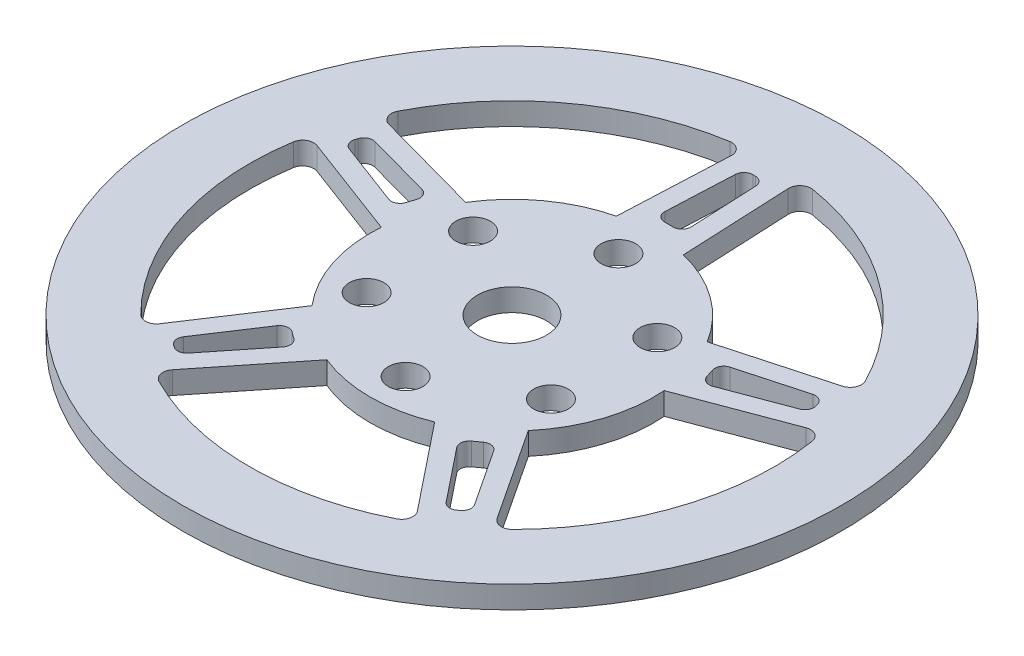
SolidWorks part; units mm, degrees
ref_plane "Front Plane" through (0, 0, 0) normal (0, 0, 1) x (1, 0, 0)
ref_plane "Top Plane" through (0, 0, 0) normal (0, 1, 0) x (1, 0, 0)
ref_plane "Right Plane" through (0, 0, 0) normal (1, 0, 0) x (0, 0, -1)
sketch "Sketch1" plane through (0, 0, 0) normal (0, 1, 0) x (1, 0, 0)
  line L0 (0, 0) -> (0, -9.525) construction
  line L1 (0, 0) -> (8.2489, -4.7625) construction
  line L2 (0, 0) -> (8.2489, 4.7625) construction
  line L3 (0, 0) -> (0, 33.015) construction
  line L4 (0, 0) -> (31.3992, 10.2022) construction
  line L5 (0, 0) -> (19.4058, -26.7097) construction
  line L6 (0, 0) -> (-19.4058, -26.7097) construction
  line L7 (0, 0) -> (-31.3992, 10.2022) construction
  line L8 (-2.5, 23.3666) -> (2.5, 23.3666) construction
  line L9 (-3, 12.3406) -> (3, 12.3406) construction
  line L10 (-2.5, 23.3666) -> (-3, 12.3406)
  line L11 (2.5, 23.3666) -> (3, 12.3406)
  line L12 (-0.8753, 21.6666) -> (0.8753, 21.6666)
  line L13 (0.8753, 21.6666) -> (1.2212, 14.0406)
  line L14 (1.2212, 14.0406) -> (-1.2212, 14.0406)
  line L15 (-1.2212, 14.0406) -> (-0.8753, 21.6666)
  line L16 (21.4505, 9.5983) -> (10.8095, 6.6666)
  line L17 (12.976, 5.5002) -> (20.3357, 7.5279)
  line L18 (20.8767, 5.8629) -> (13.7307, 3.1774)
  line L19 (20.3357, 7.5279) -> (20.8767, 5.8629)
  line L20 (13.7307, 3.1774) -> (12.976, 5.5002)
  line L21 (22.9955, 4.843) -> (12.6636, 0.9603)
  line L22 (15.7571, -17.4345) -> (9.6807, -8.2204)
  line L23 (9.2408, -10.6413) -> (13.4435, -17.0142)
  line L24 (12.0272, -18.0432) -> (7.2649, -12.0769)
  line L25 (13.4435, -17.0142) -> (12.0272, -18.0432)
  line L26 (7.2649, -12.0769) -> (9.2408, -10.6413)
  line L27 (11.712, -20.3735) -> (4.8266, -11.7471)
  line L28 (-11.712, -20.3735) -> (-4.8266, -11.7471)
  line L29 (-7.2649, -12.0769) -> (-12.0272, -18.0432)
  line L30 (-13.4435, -17.0142) -> (-9.2408, -10.6413)
  line L31 (-12.0272, -18.0432) -> (-13.4435, -17.0142)
  line L32 (-9.2408, -10.6413) -> (-7.2649, -12.0769)
  line L33 (-15.7571, -17.4345) -> (-9.6807, -8.2204)
  line L34 (-22.9955, 4.843) -> (-12.6636, 0.9603)
  line L35 (-13.7307, 3.1774) -> (-20.8767, 5.8629)
  line L36 (-20.3357, 7.5279) -> (-12.976, 5.5002)
  line L37 (-20.8767, 5.8629) -> (-20.3357, 7.5279)
  line L38 (-12.976, 5.5002) -> (-13.7307, 3.1774)
  line L39 (-21.4505, 9.5983) -> (-10.8095, 6.6666)
  line L40 (0, 0) -> (-8.2489, -4.7625) construction
  line L41 (0, 0) -> (-8.2489, 4.7625) construction
  circle A0 centre (0, 0) radius 12.7 construction
  circle A1 centre (0, 9.525) radius 1.55
  circle A2 centre (-8.2489, 4.7625) radius 1.55
  circle A3 centre (-8.2489, -4.7625) radius 1.55
  circle A4 centre (0, -9.525) radius 1.55
  circle A5 centre (0, 0) radius 29.5
  circle A6 centre (8.2489, 4.7625) radius 1.55
  circle A7 centre (0, 0) radius 3.1
  circle A8 centre (8.2489, -4.7625) radius 1.55
  circle A9 centre (0, 0) radius 23.5 construction
  arc A10 (-3, 12.3406) -> (-10.8095, 6.6666) centre (0, 0) ccw
  arc A11 (10.8095, 6.6666) -> (3, 12.3406) centre (0, 0) ccw
  arc A12 (9.6807, -8.2204) -> (12.6636, 0.9603) centre (0, 0) ccw
  arc A13 (4.8266, -11.7471) -> (-4.8266, -11.7471) centre (0, 0) cw
  arc A14 (-12.6636, 0.9603) -> (-9.6807, -8.2204) centre (0, 0) ccw
  arc A15 (-21.4505, 9.5983) -> (-2.5, 23.3666) centre (0, 0) cw
  arc A16 (2.5, 23.3666) -> (21.4505, 9.5983) centre (0, 0) cw
  arc A17 (22.9955, 4.843) -> (15.7571, -17.4345) centre (0, 0) cw
  arc A18 (11.712, -20.3735) -> (-11.712, -20.3735) centre (0, 0) cw
  arc A19 (-15.7571, -17.4345) -> (-22.9955, 4.843) centre (0, 0) cw
  point P25 (0, 0)
  point P66 (0, 0)
  dimension "D1" = 3.1
  dimension "D2" = 3.1
  dimension "D5" = 59
  dimension "D6" = 47
  dimension "D9" = 25.4
  dimension "D16" = 6.2
  dimension "D17" = 3.1
  dimension "D18" = 3.1
  dimension "D19" = 3.1
  dimension "D20" = 3.1
  dimension "D21" = 9.525
  dimension "D3" = 60
  dimension "D4" = 60
  dimension "D8" = 2.5
  dimension "D10" = 3
  dimension "D11" = 1.7
  dimension "D12" = 9.525
  dimension "D13" = 1.7
  dimension "D14" = 1.7
  dimension "D22" = 9.525
  dimension "D23" = 9.525
  dimension "D24" = 9.525
  dimension "D25" = 9.525
  dimension "D26" = 60
  dimension "D27" = 60
  dimension "D7" = 5
  dimension "D15" = 5
extrude "Boss-Extrude1" add sketch "Sketch1" along normal blind 2
fillet "Fillet2" radius 1 10 edges at (-15.7571, 1, 17.4345) (-11.712, 1, 20.3735) (11.712, 1, 20.3735) (15.7571, 1, 17.4345) (22.9955, 1, -4.843) (21.4505, 1, -9.5983) (2.5, 1, -23.3666) (-2.5, 1, -23.3666) (-22.9955, 1, -4.843) (-21.4505, 1, -9.5983)
fillet "Fillet3" radius 0.8 20 edges at (-20.8767, 1, -5.8629) (-20.3357, 1, -7.5279) (-12.976, 1, -5.5002) (-13.7307, 1, -3.1774) (-12.0272, 1, 18.0432) (-13.4435, 1, 17.0142) (-9.2408, 1, 10.6413) (-7.2649, 1, 12.0769) (13.4435, 1, 17.0142) (12.0272, 1, 18.0432) (7.2649, 1, 12.0769) (9.2408, 1, 10.6413) (12.976, 1, -5.5002) (20.3357, 1, -7.5279) (20.8767, 1, -5.8629) (13.7307, 1, -3.1774) (-0.8753, 1, -21.6666) (0.8753, 1, -21.6666) (-1.2212, 1, -14.0406) (1.2212, 1, -14.0406)
